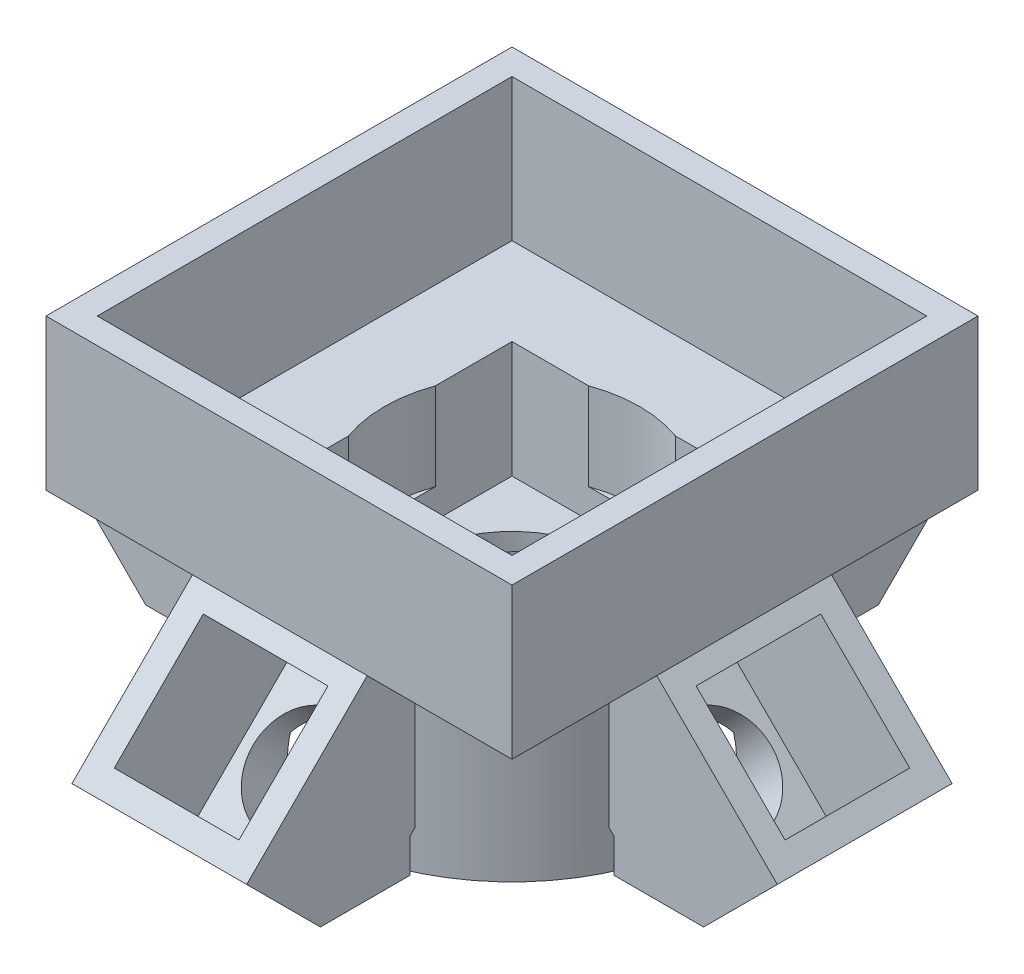
SolidWorks part; units mm, degrees
material "AISI 321 Annealed Stainless Steel (SS)"
ref_plane "前视基准面" through (0, 0, 0) normal (0, 0, 1) x (1, 0, 0)
ref_plane "上视基准面" through (0, 0, 0) normal (0, 1, 0) x (1, 0, 0)
ref_plane "右视基准面" through (0, 0, 0) normal (1, 0, 0) x (0, 0, -1)
other "Configuration Table"
sketch "Sketch6" plane through (0, 0, 0) normal (0, 1, 0) x (1, 0, 0)
  circle A0 centre (0, 0) radius 2.19
  circle A1 centre (0, 0) radius 3
  dimension "D1" = 4.38
  dimension "D2" = 6
extrude "Boss-Extrude3" add sketch "Sketch6" along normal blind 2
sketch "Sketch7" plane through (0, 0, 0) normal (0, -1, 0) x (-1, 0, 0)
  line L1 (-2.06, -2.06) -> (2.06, -2.06)
  line L2 (-2.06, -2.06) -> (-2.06, 2.06)
  line L3 (-2.06, 2.06) -> (2.06, 2.06)
  line L4 (2.06, -2.06) -> (2.06, 2.06)
  line L5 (-2.06, -2.06) -> (2.06, 2.06) construction
  line L6 (-2.06, 2.06) -> (2.06, -2.06) construction
  line L11 (-2.25, -2.25) -> (2.25, 2.25) construction
  line L12 (-2.25, 2.25) -> (2.25, -2.25) construction
  point P0 (0, 0)
  point P6 (0, 0)
  dimension "D2" = 4.12
  dimension "D4" = 4.5
extrude "Cut-Extrude2" cut sketch "Sketch7" against normal blind 0.5
sketch "Sketch8" plane through (0, 0.5, 0) normal (0, -1, 0) x (-1, 0, 0)
  line L1 (-0.7433, 2.06) -> (0.7433, 2.06)
  line L2 (-2.06, 0.7433) -> (-2.06, -0.7433)
  line L3 (-0.7433, -2.06) -> (0.7433, -2.06)
  line L4 (2.06, 0.7433) -> (2.06, -0.7433)
  arc A0 (-2.06, 0.7433) -> (-2.06, -0.7433) centre (0, 0) ccw
  arc A1 (0.7433, 2.06) -> (-0.7433, 2.06) centre (0, 0) ccw
  arc A2 (2.06, -0.7433) -> (2.06, 0.7433) centre (0, 0) ccw
  arc A3 (-0.7433, -2.06) -> (0.7433, -2.06) centre (0, 0) ccw
extrude "Boss-Extrude5" add sketch "Sketch8" along normal blind 0.5
sketch "Sketch9" plane through (0, 0, 0) normal (0, 0, 1) x (1, 0, 0)
  line L0 (0, 2.7565) -> (0, -2.7704) construction
  line L1 (-3.7455, 0) -> (3.8358, 0) construction
  line L2 (2.19, 2.4224) -> (2.19, 0) construction
  line L3 (-2.19, 2) -> (-2.19, 0) construction
sketch "Sketch13" plane through (0, 0, 0) normal (0, -1, 0) x (-1, 0, 0)
  line L0 (-2.06, 2.06) -> (2.06, -2.06) construction
sketch "Sketch17" plane through (0, 0, 0) normal (0, -1, 0) x (-1, 0, 0)
  line L0 (-2.06, 2.06) -> (2.06, -2.06) construction
  circle A0 centre (0, 0) radius 3
  circle A1 centre (0, 0) radius 3.5
  dimension "D1" = 6
  dimension "D2" = 0.5
extrude "Boss-Extrude11" add sketch "Sketch17" against normal blind 0.5
sketch "Sketch18" plane through (0, 0, 0) normal (0, -1, 0) x (-1, 0, 0)
  circle A0 centre (0, 0) radius 3.1
  circle A1 centre (0, 0) radius 3.5
  dimension "D1" = 6.2
  dimension "D2" = 7
extrude "Boss-Extrude12" add sketch "Sketch18" along normal blind 2
sketch "Sketch19" plane through (0, 0, 0) normal (0, 0, 1) x (1, 0, 0)
  line L1 (2.19, 2.4224) -> (2.19, 0) construction
  line L2 (4.2889, -2) -> (5.1213, -1.1675)
  line L3 (5.1213, -1.1675) -> (3, 0.9538)
  line L4 (3, 0.5) -> (3, 2) construction
  line L5 (3, 0.9538) -> (2.19, 0.1438)
  line L8 (2.19, 0.1438) -> (3.2507, -0.9169)
  line L10 (4.2889, -2) -> (4.0338, -2)
  line L12 (4.0338, -2) -> (3.2507, -2)
  line L13 (3.2507, -2) -> (3.2507, -0.9169)
  line L14 (-3.5, -2) -> (3.5, -2) construction
  dimension "D1" = 3
  dimension "D2" = 0
  dimension "D3" = 135
  dimension "D4" = 45
  dimension "D5" = 90
  dimension "D6" = 135
  dimension "D7" = 1.8562
  dimension "D8" = 1.5
extrude "Boss-Extrude13" add sketch "Sketch19" along normal blind 1.5 and the other way blind 1.5
sketch "Sketch29" plane through (1.9769, 1.9769, 0) normal (0.7071, 0.7071, 0) x (0, 0, -1)
  line L0 (1.5, -1.4469) -> (0, -1.4469) construction
  line L1 (1.5, -4.4469) -> (-1.5, -4.4469)
  line L2 (1.5, -4.4469) -> (1.5, -1.4469)
  line L3 (1.5, -1.4469) -> (-1.5, -1.4469)
  line L4 (-1.5, -4.4469) -> (-1.5, -1.4469)
  line L5 (-1.5, -1.8825) -> (-1.5, -2.8219) construction
  dimension "D1" = 0
  dimension "D2" = 0
extrude "Boss-Extrude16" add sketch "Sketch29" along normal blind 1.5
sketch "Sketch30" plane through (3.0376, 3.0376, 0) normal (0.7071, 0.7071, 0) x (0, 0, -1)
  line L0 (1.5, -1.4469) -> (-1.5, -1.4469) construction
  line L1 (-1.06, -1.8869) -> (1.06, -1.8869)
  line L2 (-1.06, -1.8869) -> (-1.06, -4.0069)
  line L3 (-1.06, -4.0069) -> (1.06, -4.0069)
  line L4 (1.06, -1.8869) -> (1.06, -4.0069)
  line L5 (-1.5, -4.4469) -> (1.5, -4.4469) construction
  line L6 (-1.5, -1.4469) -> (-1.5, -4.4469) construction
  line L7 (1.5, -4.4469) -> (1.5, -1.4469) construction
  dimension "D1" = 0.44
  dimension "D2" = 0.44
  dimension "D3" = 0.44
  dimension "D4" = 0.44
extrude "Cut-Extrude10" cut sketch "Sketch30" against normal up to surface (2.6455 mm away) up to face at (2.6201, -0.2863, 0)
sketch "Sketch31" plane through (1.1669, 1.1669, 0) normal (-0.7071, -0.7071, 0) x (0, 0, 1)
  line L0 (-1.06, -2.4696) -> (-1.06, -1.8869) construction
  line L1 (-1.16, -1.7869) -> (1.06, -1.7869)
  line L2 (-1.16, -1.7869) -> (-1.16, -4.0069)
  line L3 (-1.16, -4.0069) -> (1.06, -4.0069)
  line L4 (1.06, -1.7869) -> (1.06, -4.0069)
  line L5 (-1.06, -1.8869) -> (1.06, -1.8869) construction
  dimension "D1" = 0.1
  dimension "D2" = 0.1
  dimension "D3" = 2.22
  dimension "D4" = 2.22
extrude "Boss-Extrude17" add sketch "Sketch31" against normal blind 1.27
sketch "Sketch32" plane through (2.0649, 2.0649, 0) normal (0.7071, 0.7071, 0) x (0, 0, -1)
  line L0 (-1.06, -4.0069) -> (1.06, -4.0069) construction
  line L1 (1.06, -4.0069) -> (1.06, -1.8869) construction
  circle A0 centre (0, -2.9469) radius 0.89
  dimension "D1" = 1.78
  dimension "D2" = 1.06
  dimension "D3" = 1.06
extrude "Cut-Extrude11" cut sketch "Sketch32" against normal through all both and the other way through all
ref_point "Point3"
sketch "Sketch33" plane through (3.0376, 3.0376, 0) normal (0.7071, 0.7071, 0) x (0, 0, -1)
  line L0 (1.5, -4.4469) -> (1.5, -1.4469) construction
  line L1 (1.6, -1.3469) -> (-1.6, -1.3469)
  line L2 (1.6, -1.3469) -> (1.6, -4.5469)
  line L3 (1.6, -4.5469) -> (-1.6, -4.5469)
  line L4 (-1.6, -1.3469) -> (-1.6, -4.5469)
  line L5 (1.5, -1.4469) -> (-1.5, -1.4469) construction
  line L6 (-1.5, -4.4469) -> (1.5, -4.4469) construction
  dimension "D1" = 0.1
  dimension "D2" = 0.1
  dimension "D3" = 0.1
  dimension "D4" = 3.2
extrude "Cut-Extrude12" cut sketch "Sketch33" against normal blind 0.18
pattern_circular "CirPattern3" count 4 over 360 about axis through (0, 0, 0) along (0, 1, 0) of "Boss-Extrude13", "Boss-Extrude16"
sketch "Sketch34" plane through (-3.0376, 3.0376, 0) normal (-0.7071, 0.7071, 0) x (0, 0, 1)
  line L0 (1.5, -1.4469) -> (-1.5, -1.4469) construction
  line L1 (-1.06, -1.8869) -> (1.06, -1.8869)
  line L2 (-1.06, -1.8869) -> (-1.06, -4.0069)
  line L3 (-1.06, -4.0069) -> (1.06, -4.0069)
  line L4 (1.06, -1.8869) -> (1.06, -4.0069)
  line L5 (-1.5, -4.4469) -> (1.5, -4.4469) construction
  line L6 (1.5, -4.4469) -> (1.5, -1.4469) construction
  line L7 (-1.5, -1.4469) -> (-1.5, -4.4469) construction
  dimension "D1" = 0.44
  dimension "D2" = 0.44
  dimension "D3" = 0.44
  dimension "D4" = 0.44
extrude "Cut-Extrude13" cut sketch "Sketch34" against normal up to surface (2.6455 mm away) up to face at (-2.6201, -0.2863, 0)
sketch "Sketch35" plane through (0, 3.0376, -3.0376) normal (0, 0.7071, -0.7071) x (1, 0, 0)
  line L0 (1.5, 4.4469) -> (-1.5, 4.4469) construction
  line L1 (-1.07, 4.0269) -> (1.07, 4.0269)
  line L2 (-1.07, 4.0269) -> (-1.07, 1.8669)
  line L3 (-1.07, 1.8669) -> (1.07, 1.8669)
  line L4 (1.07, 4.0269) -> (1.07, 1.8669)
  line L5 (-1.5, 4.4469) -> (-1.5, 1.4469) construction
  line L6 (1.5, 1.4469) -> (1.5, 4.4469) construction
  line L7 (-1.5, 1.4469) -> (1.5, 1.4469) construction
  dimension "D1" = 0.42
  dimension "D2" = 0.43
  dimension "D3" = 0.43
  dimension "D4" = 0.42
extrude "Cut-Extrude14" cut sketch "Sketch35" against normal blind 2.21
sketch "Sketch36" plane through (0, 3.0376, 3.0376) normal (0, 0.7071, 0.7071) x (1, 0, 0)
  line L0 (-1.5, -1.8825) -> (-1.5, -2.8219) construction
  line L1 (-1.06, -1.8869) -> (1.06, -1.8869)
  line L2 (-1.06, -1.8869) -> (-1.06, -4.0069)
  line L3 (-1.06, -4.0069) -> (1.06, -4.0069)
  line L4 (1.06, -1.8869) -> (1.06, -4.0069)
  line L5 (-1.5, -4.4469) -> (1.5, -4.4469) construction
  line L6 (1.5, -4.4469) -> (1.5, -1.4469) construction
  line L7 (1.5, -1.4469) -> (-1.5, -1.4469) construction
  dimension "D1" = 0.44
  dimension "D2" = 0.44
  dimension "D3" = 0.44
  dimension "D4" = 0.44
extrude "Cut-Extrude15" cut sketch "Sketch36" against normal up to surface (2.6455 mm away) up to face at (0, -0.2863, 2.6201)
pattern_circular "CirPattern16" count 4 over 360 about axis through (0, 0, 0) along (0, 1, 0) of "Boss-Extrude17", "Cut-Extrude11", "Cut-Extrude12"
sketch "Sketch37" plane through (0, -2, 0) normal (0, -1, 0) x (1, 0, 0)
  circle A1 centre (0, 0) radius 10
  dimension "D2" = 20
extrude "Cut-Extrude17" cut sketch "Sketch37" against normal blind 0.5 contours A1
sketch "Sketch38" plane through (0, 0.5, 0) normal (0, 1, 0) x (1, 0, 0)
  circle A0 centre (0, 0) radius 3.5
  circle A1 centre (0, 0) radius 2.85
  dimension "D1" = 7
  dimension "D2" = 5.7
extrude "Boss-Extrude18" add sketch "Sketch38" along normal up to surface (1.5 mm away) up to face at (0, 2, 3)
sketch "Sketch39" plane through (0, 2.0649, -2.0649) normal (0, 0.7071, -0.7071) x (1, 0, 0)
  line L1 (-1.06, 4.0069) -> (1.06, 4.0069)
  line L2 (-1.06, 4.0069) -> (-1.06, 1.8869)
  line L3 (-1.06, 1.8869) -> (1.06, 1.8869)
  line L4 (1.06, 4.0069) -> (1.06, 1.8869)
extrude "Cut-Extrude18" cut sketch "Sketch39" along normal blind 0.5
sketch "Sketch40" plane through (0, 2, 0) normal (0, 1, 0) x (1, 0, 0)
  line L1 (-3.5, 3.5) -> (3.5, 3.5)
  line L2 (-3.5, 3.5) -> (-3.5, -3.5)
  line L3 (-3.5, -3.5) -> (3.5, -3.5)
  line L4 (3.5, 3.5) -> (3.5, -3.5)
  line L5 (-4, 4) -> (4, 4)
  line L6 (-4, 4) -> (-4, -4)
  line L7 (-4, -4) -> (4, -4)
  line L8 (4, 4) -> (4, -4)
  dimension "D1" = 3.5
  dimension "D2" = 3.5
  dimension "D3" = 3.5
  dimension "D4" = 3.5
  dimension "D5" = 0.5
  dimension "D6" = 0.5
  dimension "D7" = 0.5
  dimension "D8" = 0.5
extrude "Boss-Extrude19" add sketch "Sketch40" along normal blind 2.44 separate body
sketch "Sketch41" plane through (0, 2, 0) normal (0, -1, 0) x (1, 0, 0)
  line L1 (-4, 4) -> (4, 4)
  line L2 (-4, 4) -> (-4, -4)
  line L3 (-4, -4) -> (4, -4)
  line L4 (4, 4) -> (4, -4)
  circle A0 centre (0, 0) radius 2.19
  dimension "D1" = 4.38
extrude "Boss-Extrude20" add sketch "Sketch41" along normal blind 0.15
sketch "Sketch42" plane through (0, 1.85, 0) normal (0, -1, 0) x (1, 0, 0)
  line L1 (-4, 4) -> (4, 4)
  line L2 (-4, 4) -> (-4, -4)
  line L3 (-4, -4) -> (4, -4)
  line L4 (4, 4) -> (4, -4)
  circle A0 centre (0, 0) radius 2.19
  dimension "D1" = 4.38
extrude "Boss-Extrude21" add sketch "Sketch42" along normal up to vertex (0.7339 mm away) draft 45
sketch "Sketch43" plane through (0, 2, 0) normal (0, 1, 0) x (1, 0, 0)
  line L1 (-3.56, 3.56) -> (3.56, 3.56)
  line L2 (-3.56, 3.56) -> (-3.56, -3.56)
  line L3 (-3.56, -3.56) -> (3.56, -3.56)
  line L4 (3.56, 3.56) -> (3.56, -3.56)
  line L5 (-3.56, 3.56) -> (3.56, -3.56) construction
  line L6 (-3.56, -3.56) -> (3.56, 3.56) construction
  point P0 (0, 0)
  dimension "D1" = 7.12
  dimension "D2" = 7.12
extrude "Cut-Extrude19" cut sketch "Sketch43" along normal blind 10
sketch "Sketch44" plane through (0, 0.5, 0) normal (0, -1, 0) x (-1, 0, 0)
  line L1 (2.06, -2.06) -> (-2.06, -2.06)
  line L2 (2.06, -2.06) -> (2.06, 2.06)
  line L3 (2.06, 2.06) -> (-2.06, 2.06)
  line L4 (-2.06, -2.06) -> (-2.06, 2.06)
extrude "Cut-Extrude20" cut sketch "Sketch44" against normal blind 10
sketch "Sketch46" plane through (0, 0, 0) normal (0, -1, 0) x (1, 0, 0)
  line L0 (-2.3338, 1.5) -> (-2.7129, 1.5)
  line L1 (-2.3338, 1.5) -> (-2.3338, -1.5)
  line L2 (-2.3338, -1.5) -> (-2.7129, -1.5)
  line L3 (1.5, 2.3338) -> (1.5, 2.7129)
  line L4 (1.5, 2.3338) -> (-1.5, 2.3338)
  line L5 (-1.5, 2.3338) -> (-1.5, 2.7129)
  line L6 (2.3338, -1.5) -> (2.7129, -1.5)
  line L7 (2.3338, -1.5) -> (2.3338, 1.5)
  line L8 (2.3338, 1.5) -> (2.7129, 1.5)
  line L9 (-1.5, -2.3338) -> (-1.5, -2.7129)
  line L10 (-1.5, -2.3338) -> (1.5, -2.3338)
  line L11 (1.5, -2.3338) -> (1.5, -2.7129)
  arc A0 (-2.7129, -1.5) -> (-1.5, -2.7129) centre (0, 0) ccw
  arc A1 (-1.5, 2.7129) -> (-2.7129, 1.5) centre (0, 0) ccw
  arc A2 (2.7129, 1.5) -> (1.5, 2.7129) centre (0, 0) ccw
  arc A3 (1.5, -2.7129) -> (2.7129, -1.5) centre (0, 0) ccw
  point P26 (0, 0)
  dimension "D1" = 4
extrude "Boss-Extrude22" add sketch "Sketch46" along normal blind 0.3
sketch "Sketch47" plane through (0, -0.3, 0) normal (0, -1, 0) x (1, 0, 0)
  line L0 (0, 0) -> (-2.0435, 0) construction
  circle A0 centre (0, 0) radius 1.75
  dimension "D1" = 3.5
extrude "Cut-Extrude21" cut sketch "Sketch47" against normal blind 4.3
sketch "Sketch48" plane through (0, 0, 0) normal (1, 0, 0) x (0, 0, -1)
  line L0 (0, -1.7884) -> (0, 4.7197) construction
pattern_circular "CirPattern22" count 4 over 360 about axis through (0, 0, 0) along (0, 1, 0) of "Cut-Extrude14"
